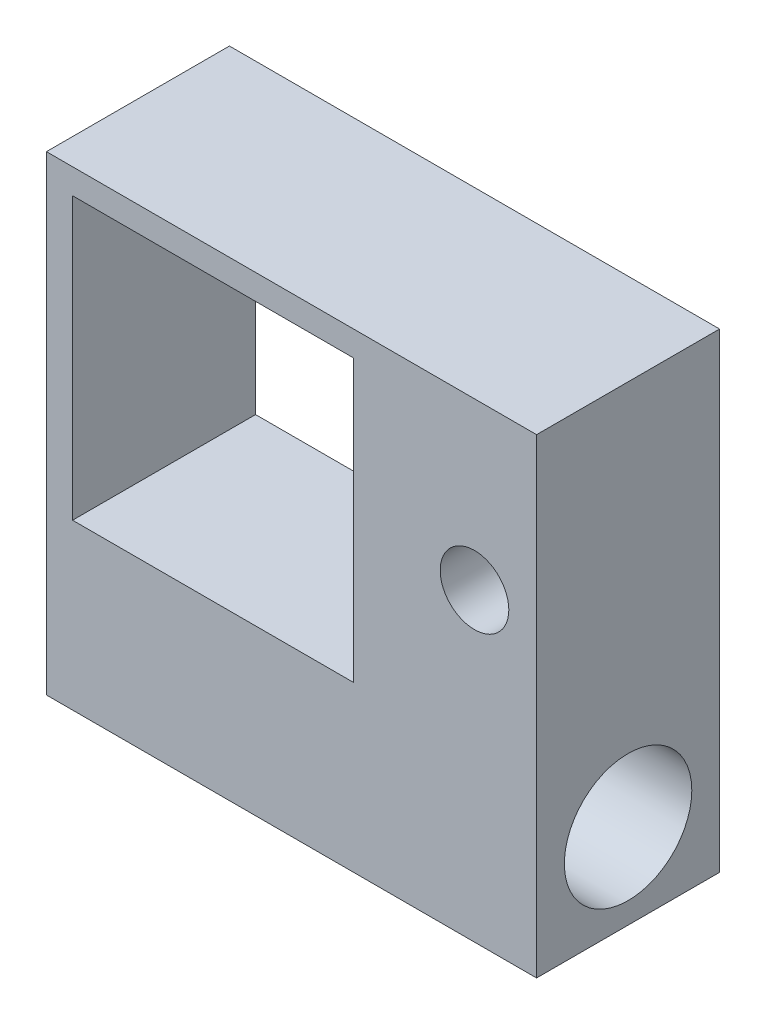
SolidWorks part; units mm, degrees
ref_plane "Front Plane" through (0, 0, 0) normal (0, 0, 1) x (1, 0, 0)
ref_plane "Top Plane" through (0, 0, 0) normal (0, 1, 0) x (1, 0, 0)
ref_plane "Right Plane" through (0, 0, 0) normal (1, 0, 0) x (0, 0, -1)
sketch "Sketch1" plane through (0, 0, 0) normal (0, 0, 1) x (1, 0, 0)
  line L0 (9.5, 32.16) -> (-33.5, -10.84) construction
  line L1 (-37.5, -36) -> (37.5, -36)
  line L2 (-37.5, -36) -> (-37.5, 36)
  line L3 (-37.5, 36) -> (37.5, 36)
  line L4 (37.5, -36) -> (37.5, 36)
  line L5 (-37.5, -36) -> (37.5, 36) construction
  line L6 (-37.5, 36) -> (37.5, -36) construction
  line L7 (-33.5, 32.16) -> (9.5, 32.16)
  line L8 (-33.5, 32.16) -> (-33.5, -10.84)
  line L9 (-33.5, -10.84) -> (9.5, -10.84)
  line L10 (9.5, 32.16) -> (9.5, -10.84)
  line L11 (-33.5, 32.16) -> (9.5, -10.84) construction
  circle A0 centre (28, 10.66) radius 5.25
  point P0 (0, 0)
  point P12 (9.5, 10.66)
  point P13 (-12, 10.66)
  dimension "D3" = 10.5
  dimension "D7" = 9.5
  dimension "D1" = 75
  dimension "D2" = 72
  dimension "D4" = 43
  dimension "D5" = 4
  dimension "D8" = 0
  dimension "D9" = 3.84
  dimension "D10" = 40
  dimension "D11" = 43
extrude "Boss-Extrude1" add sketch "Sketch1" along normal blind 28
sketch "Sketch2" plane through (37.5, 0, 0) normal (1, 0, 0) x (0, 0, -1)
  line L0 (-28, -36) -> (0, -36) construction
  circle A0 centre (-14, -23) radius 9.75
  dimension "D1" = 19.5
  dimension "D2" = 13
extrude "Cut-Extrude1" cut sketch "Sketch2" against normal through all
